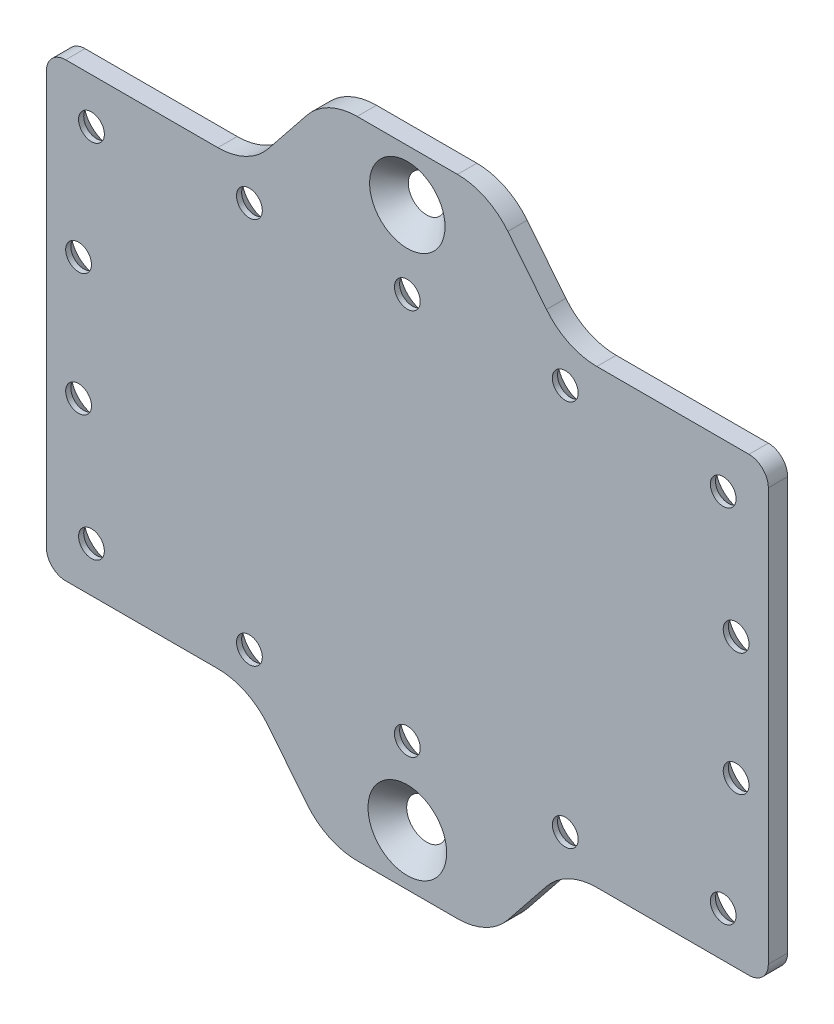
SolidWorks part; units mm, degrees
material "6063-O"
ref_plane "Front Plane" through (0, 0, 0) normal (0, 0, 1) x (1, 0, 0)
ref_plane "Top Plane" through (0, 0, 0) normal (0, 1, 0) x (1, 0, 0)
ref_plane "Right Plane" through (0, 0, 0) normal (1, 0, 0) x (0, 0, -1)
sketch "Sketch1" plane through (0, 0, 0) normal (0, 0, 1) x (1, 0, 0)
  line L1 (-42.6192, 55.8813) -> (63.3808, 55.8813)
  line L2 (-45.6192, 52.8813) -> (-45.6192, -41.1187)
  line L3 (-42.6192, -44.1187) -> (63.3808, -44.1187)
  line L4 (66.3808, 52.8813) -> (66.3808, -41.1187)
  arc A0 (-45.6192, -41.1187) -> (-42.6192, -44.1187) centre (-42.6192, -41.1187) ccw
  arc A1 (63.3808, -44.1187) -> (66.3808, -41.1187) centre (63.3808, -41.1187) ccw
  arc A2 (66.3808, 52.8813) -> (63.3808, 55.8813) centre (63.3808, 52.8813) ccw
  arc A3 (-45.6192, 52.8813) -> (-42.6192, 55.8813) centre (-42.6192, 52.8813) cw
  point P6 (-45.6192, -44.1187)
  point P11 (66.3808, 55.8813)
  point P14 (-45.6192, 55.8813)
  dimension "D3" = 3
  dimension "D1" = 112
  dimension "D2" = 100
extrude "Boss-Extrude1" add sketch "Sketch1" along normal blind 3
sketch "Sketch3" plane through (0, 0, 3) normal (0, 0, 1) x (1, 0, 0)
  line L2 (63.3808, 55.8813) -> (-42.6192, 55.8813) construction
  line L3 (7.2808, 55.8813) -> (13.4808, 55.8813)
  line L5 (-42.6192, -44.1187) -> (63.3808, -44.1187) construction
  line L6 (10.3808, 24.2476) -> (10.3808, -7.2931) construction
  line L8 (39.7786, 40.8813) -> (66.3808, 40.8813)
  line L9 (66.3808, -41.1187) -> (66.3808, 52.8813) construction
  line L10 (22.9721, 55.8813) -> (31.9699, 44.6343)
  line L11 (22.9721, 55.8813) -> (13.4808, 55.8813)
  line L13 (-19.0169, 40.8813) -> (-45.6192, 40.8813)
  line L14 (-2.2104, 55.8813) -> (-11.2083, 44.6343)
  line L15 (-57.8903, 5.8813) -> (91.1459, 5.8813) construction
  line L16 (39.7786, -29.1187) -> (66.3808, -29.1187)
  line L17 (22.9721, -44.1187) -> (31.9699, -32.8716)
  line L18 (-2.2104, -44.1187) -> (-11.2083, -32.8716)
  line L19 (-19.0169, -29.1187) -> (-45.6192, -29.1187)
  line L20 (-45.6192, 40.8813) -> (-45.6192, 63.9158)
  line L21 (-45.6192, 63.9158) -> (-2.2104, 63.9158)
  line L22 (-2.2104, 63.9158) -> (-2.2104, 55.8813)
  line L23 (22.9721, 63.9158) -> (22.9721, 55.8813)
  line L24 (66.3808, 40.8813) -> (66.3808, 63.9158)
  line L25 (66.3808, 63.9158) -> (22.9721, 63.9158)
  line L26 (66.3808, -29.1187) -> (66.3808, -52.1531)
  line L27 (22.9721, -52.1531) -> (22.9721, -44.1187)
  line L28 (66.3808, -52.1531) -> (22.9721, -52.1531)
  line L29 (-45.6192, -29.1187) -> (-45.6192, -52.1531)
  line L30 (-2.2104, -52.1531) -> (-2.2104, -44.1187)
  line L31 (-45.6192, -52.1531) -> (-2.2104, -52.1531)
  circle A1 centre (10.3808, -36.1187) radius 3
  arc A2 (39.7786, 40.8813) -> (31.9699, 44.6343) centre (39.7786, 50.8813) cw
  arc A3 (-19.0169, 40.8813) -> (-11.2083, 44.6343) centre (-19.0169, 50.8813) ccw
  arc A4 (39.7786, -29.1187) -> (31.9699, -32.8716) centre (39.7786, -39.1187) ccw
  arc A5 (-19.0169, -29.1187) -> (-11.2083, -32.8716) centre (-19.0169, -39.1187) cw
  circle A6 centre (10.3808, 47.8813) radius 3
  arc M1 (-45.6192, -41.1187) -> (-42.6192, -44.1187) centre (-42.6192, -41.1187) ccw
  line M2 (-42.6192, -44.1187) -> (63.3808, -44.1187)
  arc M3 (63.3808, -44.1187) -> (66.3808, -41.1187) centre (63.3808, -41.1187) ccw
  line M4 (66.3808, -41.1187) -> (66.3808, 52.8813)
  arc M5 (66.3808, 52.8813) -> (63.3808, 55.8813) centre (63.3808, 52.8813) ccw
  line M6 (63.3808, 55.8813) -> (-42.6192, 55.8813)
  arc M7 (-42.6192, 55.8813) -> (-45.6192, 52.8813) centre (-42.6192, 52.8813) ccw
  line M8 (-45.6192, 52.8813) -> (-45.6192, -41.1187)
  dimension "D4" = 8
  dimension "D5" = 10
  dimension "D1" = 6
  dimension "D6" = 50
  dimension "D7" = 35
extrude "Cut-Extrude1" cut sketch "Sketch3" against normal blind 10 contours L22 L21 L20 M7 M6 | L13 A3 L14 M6 M7 M8 | L24 L25 L23 M6 M5 | A2 L8 L10 M4 M5 M6 | L16 A4 L17 M2 M3 M4 | L28 L26 L27 M3 M2 | A5 L19 L18 M8 M1 M2 | L29 L31 L30 M2 M1 | A1 | A1 region at (-24.0306, 59.8727, 3) region at (-26.7626, 48.8017, 3) region at (47.5243, 48.8017, 3) region at (44.7923, 59.8727, 3) region at (-26.7626, -37.0391, 3) region at (47.5243, -37.0391, 3) region at (-24.0306, -48.1101, 3) region at (44.7923, -48.1101, 3) region at (10.3808, -36.1187, 3)
fillet "Fillet1" radius 10 4 edges at (-2.2104, 55.8813, 1.5) (22.9721, 55.8813, 1.5) (-2.2104, -44.1187, 1.5) (22.9721, -44.1187, 1.5)
fillet "Fillet2" radius 3 4 edges at (-45.6192, 40.8813, 1.5) (-45.6192, -29.1187, 1.5) (66.3808, 40.8813, 1.5) (66.3808, -29.1187, 1.5)
sketch "Sketch6" plane through (0, 0, 3) normal (0, 0, 1) x (1, 0, 0)
  line L0 (18.1659, 55.8813) -> (2.5958, 55.8813) construction
  line L1 (-45.6192, 37.8813) -> (-45.6192, -26.1187) construction
  circle A0 centre (10.3808, 47.8813) radius 2.7497
  point P4 (10.3808, 55.8813)
  dimension "D1" = 8
  dimension "D2" = 56
extrude "Cut-Extrude4" cut sketch "Sketch6" against normal blind 10
chamfer "Chamfer3" distance 3.1 angle 45 2 edges at (13.3808, -36.1187, 3) (13.1306, 47.8813, 3)
sketch "Sketch7" plane through (0, 0, 0) normal (0, 0, -1) x (-1, 0, 0)
  circle A0 centre (38.6192, -22.1187) radius 1.6
  circle A1 centre (14.1192, -24.1187) radius 1.6
  circle A2 centre (-10.3808, -24.1187) radius 1.6
  circle A3 centre (-34.8808, -24.1187) radius 1.6
  circle A4 centre (-59.3808, -22.1187) radius 1.6
  circle A5 centre (-61.3808, -3.6187) radius 1.6
  circle A6 centre (-61.3808, 15.3813) radius 1.6
  circle A7 centre (-59.3808, 33.8813) radius 1.6
  circle A8 centre (-34.8808, 35.8813) radius 1.6
  circle A9 centre (-10.3808, 35.8813) radius 1.6
  circle A10 centre (14.1192, 35.8813) radius 1.6
  circle A11 centre (38.6192, 33.8813) radius 1.6
  circle A12 centre (40.6192, 15.3813) radius 1.6
  circle A13 centre (40.6192, -3.6187) radius 1.6
  circle A14 centre (38.6192, -22.1187) radius 1.6 construction
  circle A15 centre (40.6192, -3.6187) radius 1.6 construction
  circle A16 centre (14.1192, -24.1187) radius 1.6 construction
  circle A17 centre (-10.3808, -24.1187) radius 1.6 construction
  circle A18 centre (-34.8808, -24.1187) radius 1.6 construction
  circle A19 centre (-59.3808, -22.1187) radius 1.6 construction
  circle A20 centre (40.6192, 15.3813) radius 1.6 construction
  circle A21 centre (38.6192, 33.8813) radius 1.6 construction
  circle A22 centre (14.1192, 35.8813) radius 1.6 construction
  circle A23 centre (-10.3808, 35.8813) radius 1.6 construction
  circle A24 centre (-34.8808, 35.8813) radius 1.6 construction
  circle A25 centre (-59.3808, 33.8813) radius 1.6 construction
  circle A26 centre (-61.3808, 15.3813) radius 1.6 construction
  circle A27 centre (-61.3808, -3.6187) radius 1.6 construction
extrude "Cut-Extrude5" cut sketch "Sketch7" against normal up to next
sketch "Sketch8" plane through (0, 0, 0) normal (0, 0, -1) x (-1, 0, 0)
  circle A0 centre (-59.3808, 33.8813) radius 2
  circle A1 centre (-34.8808, 35.8813) radius 2
  circle A2 centre (-10.3808, 35.8813) radius 2
  circle A3 centre (14.1192, 35.8813) radius 2
  circle A4 centre (38.6192, 33.8813) radius 2
  circle A5 centre (40.6192, 15.3813) radius 2
  circle A6 centre (38.6192, -22.1187) radius 2
  circle A7 centre (40.6192, -3.6187) radius 2
  circle A8 centre (14.1192, -24.1187) radius 2
  circle A9 centre (-10.3808, -24.1187) radius 2
  circle A10 centre (-34.8808, -24.1187) radius 2
  circle A11 centre (-59.3808, -22.1187) radius 2
  circle A12 centre (-61.3808, -3.6187) radius 2
  circle A13 centre (-61.3808, 15.3813) radius 2
  dimension "D1" = 4
extrude "Cut-Extrude6" cut sketch "Sketch8" against normal through all
chamfer "Chamfer4" distance 2.2 angle 45 14 edges at (-16.1192, -24.1187, 0) (8.3808, -24.1187, 0) (57.3808, -22.1187, 0) (32.8808, -24.1187, 0) (59.3808, -3.6187, 0) (59.3808, 15.3813, 0) (57.3808, 33.8813, 0) (32.8808, 35.8813, 0) (8.3808, 35.8813, 0) (-16.1192, 35.8813, 0) (-40.6192, 33.8813, 0) (-42.6192, 15.3813, 0) (-42.6192, -3.6187, 0) (-40.6192, -22.1187, 0)
